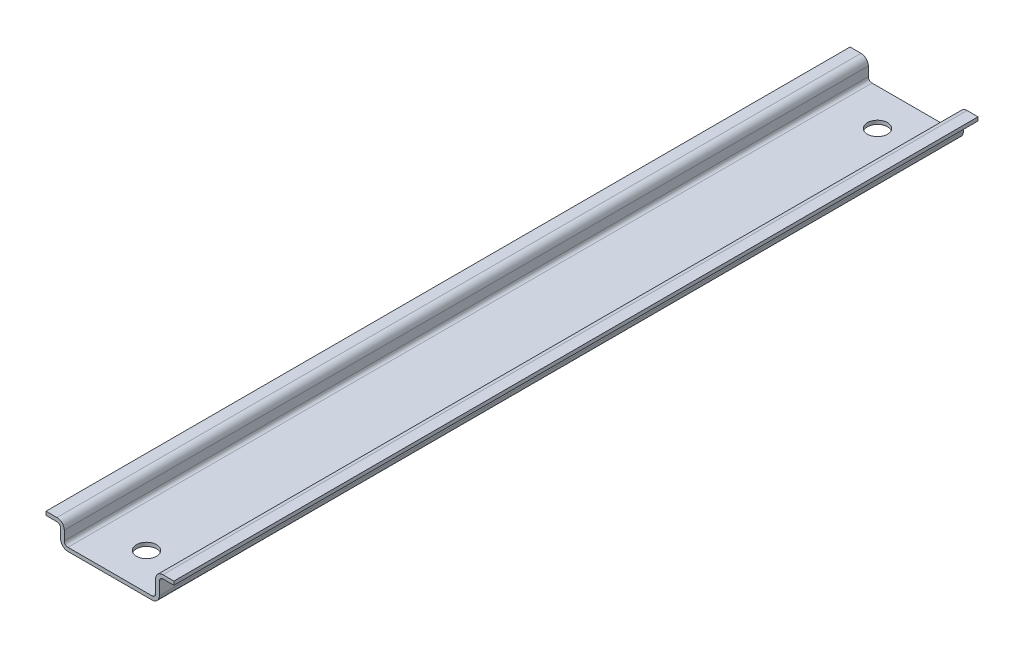
SolidWorks part; units mm, degrees
ref_plane "Front Plane" through (0, 0, 0) normal (0, 0, 1) x (1, 0, 0)
ref_plane "Top Plane" through (0, 0, 0) normal (0, 1, 0) x (1, 0, 0)
ref_plane "Right Plane" through (0, 0, 0) normal (1, 0, 0) x (0, 0, -1)
sketch "Sketch1" plane through (0, 0, 0) normal (0, 0, 1) x (1, 0, 0)
  line L0 (2, 0) -> (25, 0)
  line L1 (0, 2) -> (0, 4.5445)
  line L2 (-1, 5.5445) -> (-4, 5.5445)
  line L3 (27, 2) -> (27, 5.5)
  line L4 (28, 6.5) -> (31, 6.5)
  line L5 (-1, 6.5445) -> (-4, 6.5445)
  line L6 (1, 2) -> (1, 4.5445)
  line L7 (2, 1) -> (25, 1)
  line L8 (26, 2) -> (26, 5.5)
  line L9 (28, 7.5) -> (31, 7.5)
  line L10 (-4, 5.5445) -> (-4, 6.5445)
  line L11 (31, 6.5) -> (31, 7.5)
  line L12 (27, 0) -> (27, 6.5) construction
  line L13 (27, 6.5) -> (31, 6.5) construction
  line L14 (1, 1) -> (26, 1) construction
  line L15 (26, 1) -> (26, 7.5) construction
  line L16 (1, 1) -> (1, 6.5445) construction
  line L17 (0, 0) -> (0, 5.5445) construction
  line L18 (0, 5.5445) -> (-4, 5.5445) construction
  line L19 (26, 7.5) -> (31, 7.5) construction
  line L20 (0, 0) -> (27, 0) construction
  line L21 (1, 6.5445) -> (-4, 6.5445) construction
  arc A0 (27, 5.5) -> (28, 6.5) centre (28, 5.5) cw
  arc A1 (25, 1) -> (26, 2) centre (25, 2) ccw
  arc A2 (1, 2) -> (2, 1) centre (2, 2) ccw
  arc A3 (0, 4.5445) -> (-1, 5.5445) centre (-1, 4.5445) ccw
  arc A4 (26, 5.5) -> (28, 7.5) centre (28, 5.5) cw
  arc A5 (25, 0) -> (27, 2) centre (25, 2) ccw
  arc A6 (2, 0) -> (0, 2) centre (2, 2) cw
  arc A7 (-1, 6.5445) -> (1, 4.5445) centre (-1, 4.5445) cw
  point P16 (27, 6.5)
  point P26 (0, 5.5445)
  dimension "D7" = 1
  dimension "D8" = 2
  dimension "D2" = 4
  dimension "D3" = 4
  dimension "D5" = 7.5
  dimension "D6" = 35
  dimension "D4" = 1
extrude "Boss-Extrude1" add sketch "Sketch1" along normal blind 220
sketch "Sketch2" plane through (0, 1, 0) normal (0, 1, 0) x (1, 0, 0)
  line L0 (25, -220) -> (2, -220) construction
  line L1 (25, 0) -> (2, 0) construction
  line L3 (2, -220) -> (2, 0) construction
  circle A0 centre (13.5, -10) radius 2.75
  circle A1 centre (13.5, -210) radius 2.75
  dimension "D2" = 10
  dimension "D3" = 5.5
  dimension "D4" = 5.5
  dimension "D1" = 10
  dimension "D5" = 11.5
  dimension "D6" = 11.5
extrude "Cut-Extrude1" cut sketch "Sketch2" against normal blind 1
